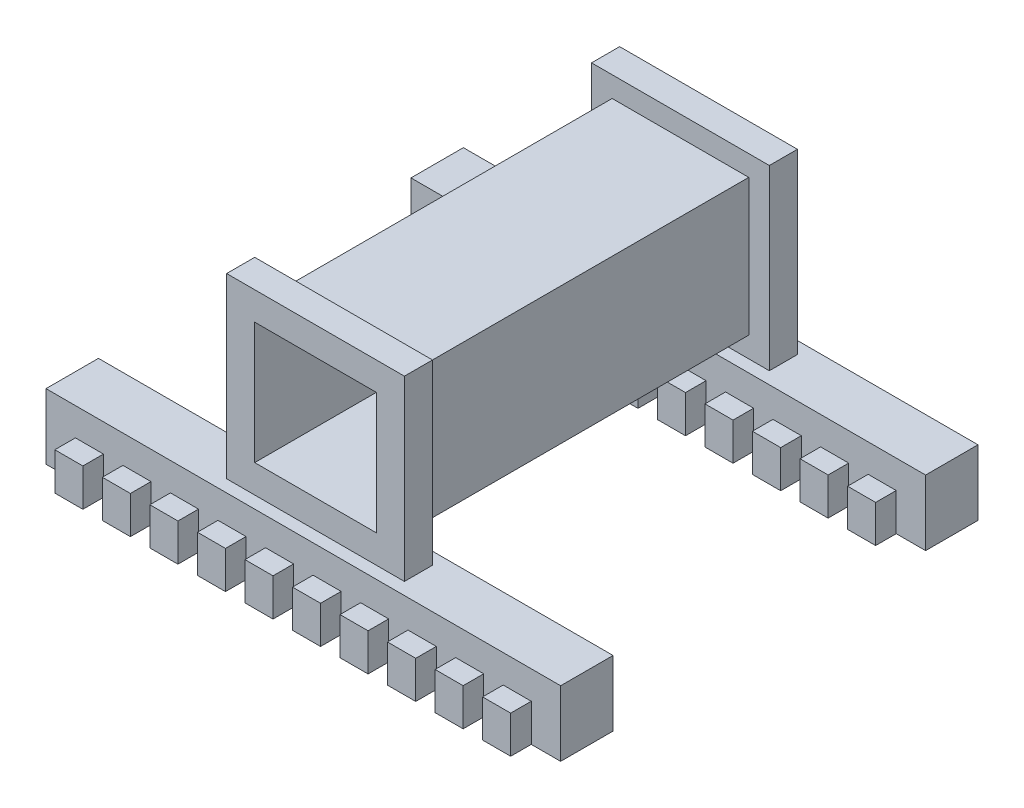
SolidWorks part; units mm, degrees
ref_plane "前视基准面" through (0, 0, 0) normal (0, 0, 1) x (1, 0, 0)
ref_plane "上视基准面" through (0, 0, 0) normal (0, 1, 0) x (1, 0, 0)
ref_plane "右视基准面" through (0, 0, 0) normal (1, 0, 0) x (0, 0, -1)
sketch "草图1" plane through (0, 0, 0) normal (0, 0, 1) x (1, 0, 0)
  line L0 (-9.5, 9.5) -> (9.5, 9.5)
  line L1 (-6.5, -6.5) -> (6.5, -6.5)
  line L2 (-6.5, -6.5) -> (-6.5, 6.5)
  line L3 (-6.5, 6.5) -> (6.5, 6.5)
  line L4 (6.5, -6.5) -> (6.5, 6.5)
  line L5 (-6.5, -6.5) -> (6.5, 6.5) construction
  line L6 (-6.5, 6.5) -> (6.5, -6.5) construction
  line L7 (9.5, -9.5) -> (9.5, 9.5)
  line L8 (-9.5, -9.5) -> (9.5, -9.5)
  line L9 (-9.5, -9.5) -> (-9.5, 9.5)
  line L10 (-7.3, 7.3) -> (7.3, 7.3)
  line L11 (7.3, -7.3) -> (7.3, 7.3)
  line L12 (-7.3, -7.3) -> (7.3, -7.3)
  line L13 (-7.3, -7.3) -> (-7.3, 7.3)
  line L15 (-27.5, -9.5) -> (27.5, -9.5)
  line L16 (-27.5, -9.5) -> (-27.5, -16.5)
  line L17 (-27.5, -16.5) -> (27.5, -16.5)
  line L18 (27.5, -9.5) -> (27.5, -16.5)
  point P0 (0, 0)
  dimension "D1" = 3
  dimension "D2" = 0.8
extrude "凸台-拉伸1" add sketch "草图1" along normal mid plane 42 contours L18 L15 L8 L16 L17 | L9 L8 L7 L0 L12 L13 L10 L11 | L13 L10 L11 L12 region at (0, 9.2313, 0) region at (0, -13, 0)
extrude "切除-拉伸1" cut sketch "草图1<3>" against normal mid plane 42 contours L2 L3 L4 L1
sketch "草图1<3>" plane through (0, 0, 0) normal (0, 0, 1) x (1, 0, 0) same geometry as "草图1"
sketch "草图2" plane through (0, 0, 0) normal (1, 0, 0) x (0, 0, -1)
  line L0 (21, -16.5) -> (21, -9.5) construction
  line L1 (21, -9.5) -> (-21, -9.5) construction
  line L2 (-21, -9.5) -> (-21, -16.5) construction
  line L3 (-21, -16.5) -> (21, -16.5) construction
  line L4 (21, -9.5) -> (21, 9.5) construction
  line L5 (21, 9.5) -> (-21, 9.5) construction
  line L6 (-21, 9.5) -> (-21, -9.5) construction
  line L7 (-21, -9.5) -> (21, -9.5) construction
  line L8 (21, -16.5) -> (21, -9.5)
  line L9 (21, -9.5) -> (-21, -9.5)
  line L10 (-21, -9.5) -> (-21, -16.5)
  line L11 (-21, -16.5) -> (21, -16.5)
  line L12 (21, -9.5) -> (21, 9.5)
  line L13 (21, 9.5) -> (-21, 9.5)
  line L14 (-21, 9.5) -> (-21, -9.5)
  line L15 (-21, -9.5) -> (21, -9.5)
extrude "切除-拉伸6" cut sketch "草图1<12>" against normal mid plane 36 contours L1 L4 L3 L2 | L9 L0 L7 L8 | L13 L10 L11 L12 region at (0, 0, 0)
sketch "草图1<12>" plane through (0, 0, 0) normal (0, 0, 1) x (1, 0, 0) same geometry as "草图1"
extrude "切除-拉伸7" cut sketch "草图1<13>" against normal mid plane 29 contours L18 L15 L8 L16 L17 region at (0, -13, 0)
sketch "草图1<13>" plane through (0, 0, 0) normal (0, 0, 1) x (1, 0, 0) same geometry as "草图1"
sketch "草图4" plane through (0, 0, 0) normal (1, 0, 0) x (0, 0, -1)
  line L0 (-21, -9.5) -> (-14.5, -9.5) construction
  line L1 (-14.5, -9.5) -> (-14.5, -16.5) construction
  line L2 (-14.5, -16.5) -> (-21, -16.5) construction
  line L3 (-21, -16.5) -> (-21, -9.5) construction
  line L4 (-18, 9.5) -> (-18, -9.5) construction
  line L5 (-18, -9.5) -> (-21, -9.5) construction
  line L6 (-21, -9.5) -> (-21, 9.5) construction
  line L7 (-21, 9.5) -> (-18, 9.5) construction
  line L8 (-18, -7.3) -> (-18, 7.3) construction
  line L9 (-18, 7.3) -> (18, 7.3) construction
  line L10 (18, 7.3) -> (18, -7.3) construction
  line L11 (18, -7.3) -> (-18, -7.3) construction
  line L12 (21, -9.5) -> (18, -9.5) construction
  line L13 (18, -9.5) -> (18, 9.5) construction
  line L14 (18, 9.5) -> (21, 9.5) construction
  line L15 (21, 9.5) -> (21, -9.5) construction
  line L16 (14.5, -16.5) -> (14.5, -9.5) construction
  line L17 (14.5, -9.5) -> (21, -9.5) construction
  line L18 (21, -9.5) -> (21, -16.5) construction
  line L19 (21, -16.5) -> (14.5, -16.5) construction
  line L20 (-21, -9.5) -> (-14.5, -9.5)
  line L21 (-14.5, -9.5) -> (-14.5, -16.5)
  line L22 (-14.5, -16.5) -> (-21, -16.5)
  line L23 (-21, -16.5) -> (-21, -9.5)
  line L24 (-18, 9.5) -> (-18, -9.5)
  line L25 (-18, -9.5) -> (-21, -9.5)
  line L26 (-21, -9.5) -> (-21, 9.5)
  line L27 (-21, 9.5) -> (-18, 9.5)
  line L28 (-18, -7.3) -> (-18, 7.3)
  line L29 (-18, 7.3) -> (18, 7.3)
  line L30 (18, 7.3) -> (18, -7.3)
  line L31 (18, -7.3) -> (-18, -7.3)
  line L32 (21, -9.5) -> (18, -9.5)
  line L33 (18, -9.5) -> (18, 9.5)
  line L34 (18, 9.5) -> (21, 9.5)
  line L35 (21, 9.5) -> (21, -9.5)
  line L36 (14.5, -16.5) -> (14.5, -9.5)
  line L37 (14.5, -9.5) -> (21, -9.5)
  line L38 (21, -9.5) -> (21, -16.5)
  line L39 (21, -16.5) -> (14.5, -16.5)
  line L40 (21, -9.5) -> (24.5, -9.5)
  line L41 (24.5, -9.5) -> (24.5, -16.5)
  line L42 (24.5, -16.5) -> (21, -16.5)
  line L43 (-21, -16.5) -> (-24.5049, -16.5)
  line L44 (-24.5049, -16.5) -> (-24.5049, -9.5)
  line L45 (-24.5049, -9.5) -> (-21, -9.5)
extrude "凸台-拉伸2" add sketch "草图4" along normal mid plane 55 contours L42 L41 L40 L38 | L45 L44 L43 L23 region at (0, -13, 22.7525) region at (0, -13, -22.75)
sketch "草图5" plane through (0, 0, -24.5) normal (0, 0, -1) x (-1, 0, 0)
  line L4 (27.5, -16.5) -> (27.5, -9.5)
  line L5 (27.5, -9.5) -> (-27.5, -9.5)
  line L6 (-27.5, -9.5) -> (-27.5, -16.5)
  line L7 (-27.5, -16.5) -> (27.5, -16.5)
  line L8 (27.5, -16.5) -> (27.5, -9.5)
  line L9 (27.5, -9.5) -> (-27.5, -9.5)
  line L10 (-27.5, -9.5) -> (-27.5, -16.5)
  line L12 (-9.5, -9.5) -> (9.5, -9.5)
  line L13 (-9.5, 9.5) -> (-9.5, -9.5)
  line L14 (9.5, 9.5) -> (-9.5, 9.5)
  line L15 (9.5, -9.5) -> (9.5, 9.5)
  line L16 (-9.5, -9.5) -> (9.5, -9.5)
  line L17 (-9.5, 9.5) -> (-9.5, -9.5)
  line L18 (9.5, 9.5) -> (-9.5, 9.5)
  line L19 (9.5, -9.5) -> (9.5, 9.5)
  line L24 (-27.5, -16.5) -> (27.5, -16.5) construction
  line L37 (22.8593, -16.5) -> (27.5, -16.5)
  line L50 (-21.36, -16.5) -> (-24.36, -16.5)
  line L55 (-11.187, -12.5036) -> (-14.213, -12.5036)
  line L56 (-11.187, -12.5036) -> (-11.187, -16.5)
  line L61 (-6.12, -16.5) -> (-9.12, -16.5)
  line L62 (-6.12, -16.5) -> (-6.12, -12.5036)
  line L68 (-1.04, -16.4978) -> (-4.04, -16.4978)
  line L86 (9.12, -16.5) -> (6.12, -16.5)
  line L91 (9.12, -16.5) -> (9.12, -12.5)
  line L92 (9.12, -12.5) -> (6.12, -12.5)
  line L97 (6.12, -16.5) -> (6.12, -12.5)
  line L98 (9.12, -16.5) -> (6.12, -12.5) construction
  line L103 (-21.36, -16.5) -> (-21.36, -12.5036)
  line L104 (-21.36, -12.5036) -> (-24.36, -12.5036)
  line L105 (-24.36, -16.5) -> (-24.36, -12.5036)
  line L106 (-21.36, -16.5) -> (-24.36, -12.5036) construction
  line L107 (-21.36, -12.5036) -> (-24.36, -16.5) construction
  line L108 (-19.28, -16.5) -> (-16.28, -16.5)
  line L109 (-19.28, -16.5) -> (-19.28, -12.5036)
  line L110 (-19.28, -12.5036) -> (-16.28, -12.5036)
  line L111 (-16.28, -16.5) -> (-16.28, -12.5036)
  line L112 (-19.28, -16.5) -> (-16.28, -12.5036) construction
  line L113 (-19.28, -12.5036) -> (-16.28, -16.5) construction
  line L114 (-11.187, -16.5) -> (-14.213, -16.5)
  line L115 (-14.213, -12.5036) -> (-14.213, -16.5)
  line L116 (-11.187, -12.5036) -> (-14.213, -16.5) construction
  line L117 (-11.187, -16.5) -> (-14.213, -12.5036) construction
  line L118 (-6.12, -12.5036) -> (-9.12, -12.5036)
  line L119 (-9.12, -16.5) -> (-9.12, -12.5036)
  line L120 (-6.12, -16.5) -> (-9.12, -12.5036) construction
  line L121 (-6.12, -12.5036) -> (-9.12, -16.5) construction
  line L122 (-1.04, -16.4978) -> (-1.04, -12.4978)
  line L123 (-1.04, -12.4978) -> (-4.04, -12.4978)
  line L124 (-4.04, -16.4978) -> (-4.04, -12.4978)
  line L125 (-1.04, -16.4978) -> (-4.04, -12.4978) construction
  line L126 (-1.04, -12.4978) -> (-4.04, -16.4978) construction
  line L128 (9.12, -12.5) -> (6.12, -16.5) construction
  line L129 (4.04, -16.5) -> (1.038, -16.5)
  line L130 (4.04, -16.5) -> (4.04, -12.4956)
  line L131 (4.04, -12.4956) -> (1.038, -12.4956)
  line L132 (1.038, -16.5) -> (1.038, -12.4956)
  line L133 (4.04, -16.5) -> (1.038, -12.4956) construction
  line L134 (4.04, -12.4956) -> (1.038, -16.5) construction
  line L135 (14.2014, -16.5) -> (11.1986, -16.5)
  line L136 (14.2014, -16.5) -> (14.2014, -12.5)
  line L137 (14.2014, -12.5) -> (11.1986, -12.5)
  line L138 (11.1986, -16.5) -> (11.1986, -12.5)
  line L139 (14.2014, -16.5) -> (11.1986, -12.5) construction
  line L140 (14.2014, -12.5) -> (11.1986, -16.5) construction
  line L141 (19.28, -16.4935) -> (16.28, -16.4935)
  line L142 (19.28, -16.4935) -> (19.28, -12.4935)
  line L143 (19.28, -12.4935) -> (16.28, -12.4935)
  line L144 (16.28, -16.4935) -> (16.28, -12.4935)
  line L145 (19.28, -16.4935) -> (16.28, -12.4935) construction
  line L146 (19.28, -12.4935) -> (16.28, -16.4935) construction
  line L151 (24.3586, -16.5) -> (21.36, -16.5)
  line L152 (24.3586, -16.5) -> (24.3586, -12.487)
  line L153 (24.3586, -12.487) -> (21.36, -12.487)
  line L154 (21.36, -16.5) -> (21.36, -12.487)
  line L155 (24.3586, -16.5) -> (21.36, -12.487) construction
  line L156 (24.3586, -12.487) -> (21.36, -16.5) construction
  point P6 (-22.86, -14.5018)
  point P33 (-17.78, -14.5018)
  point P35 (-17.78, -14.5018)
  point P39 (-12.7, -14.5018)
  point P40 (-12.7, -14.5018)
  point P45 (-7.62, -14.5018)
  point P50 (-2.54, -14.4978)
  point P55 (2.539, -14.4978)
  point P60 (7.62, -14.5)
  point P65 (12.7, -14.5)
  point P70 (17.78, -14.4935)
  point P75 (22.8593, -14.4935)
  line M42 (27.5, -16.5) -> (27.5, -9.5)
  line M43 (27.5, -9.5) -> (-27.5, -9.5)
  line M44 (-27.5, -9.5) -> (-27.5, -16.5)
  line M45 (-27.5, -16.5) -> (27.5, -16.5)
  dimension "D1" = 0
  dimension "D2" = 0
extrude "切除-拉伸9" cut sketch "草图5" against normal blind 2.2 contours L154 L153 L152 L37 L9 L105 L104 L103 L109 L110 L111 L115 L55 L56 L119 L118 L62 L132 L131 L130 L97 L92 L91 L138 L137 L136 L68 L124 L123 L122 L141 L144 L143 L142 M45 M42 M43 M44 region at (0.0011, -12.3202, -24.5)
sketch "草图6" plane through (0, 0, -14.5) normal (0, 0, 1) x (1, 0, 0)
  line L0 (-16.28, -16.4935) -> (-19.28, -16.4935) construction
  line L1 (-19.28, -16.4935) -> (-19.28, -12.4935) construction
  line L2 (-19.28, -12.4935) -> (-16.28, -12.4935) construction
  line L3 (-16.28, -12.4935) -> (-16.28, -16.4935) construction
  line L4 (27.5, -16.5) -> (27.5, -9.5)
  line L5 (27.5, -9.5) -> (-27.5, -9.5)
  line L6 (-27.5, -9.5) -> (-27.5, -16.5)
  line L7 (-27.5, -16.5) -> (27.5, -16.5)
  line L8 (27.5, -16.5) -> (27.5, -9.5)
  line L9 (27.5, -9.5) -> (-27.5, -9.5)
  line L10 (-27.5, -9.5) -> (-27.5, -16.5)
  line L11 (-27.5, -16.5) -> (27.5, -16.5)
  line L12 (-21.36, -16.5) -> (-24.3586, -16.5) construction
  line L13 (-24.3586, -16.5) -> (-24.3586, -12.487) construction
  line L14 (-24.3586, -12.487) -> (-21.36, -12.487) construction
  line L15 (-21.36, -12.487) -> (-21.36, -16.5) construction
  line L16 (-11.1986, -16.5) -> (-14.2014, -16.5) construction
  line L17 (-14.2014, -16.5) -> (-14.2014, -12.5) construction
  line L18 (-14.2014, -12.5) -> (-11.1986, -12.5) construction
  line L19 (-11.1986, -12.5) -> (-11.1986, -16.5) construction
  line L20 (-6.12, -16.5) -> (-9.12, -16.5) construction
  line L21 (-9.12, -16.5) -> (-9.12, -12.5) construction
  line L22 (-9.12, -12.5) -> (-6.12, -12.5) construction
  line L23 (-6.12, -12.5) -> (-6.12, -16.5) construction
  line L24 (-1.038, -16.5) -> (-4.04, -16.5) construction
  line L25 (-4.04, -16.5) -> (-4.04, -12.4956) construction
  line L26 (-4.04, -12.4956) -> (-1.038, -12.4956) construction
  line L27 (-1.038, -12.4956) -> (-1.038, -16.5) construction
  line L28 (4.04, -16.4978) -> (1.04, -16.4978) construction
  line L29 (1.04, -16.4978) -> (1.04, -12.4978) construction
  line L30 (1.04, -12.4978) -> (4.04, -12.4978) construction
  line L31 (4.04, -12.4978) -> (4.04, -16.4978) construction
  line L32 (9.12, -16.5) -> (6.12, -16.5) construction
  line L33 (6.12, -16.5) -> (6.12, -12.5036) construction
  line L34 (6.12, -12.5036) -> (9.12, -12.5036) construction
  line L35 (9.12, -12.5036) -> (9.12, -16.5) construction
  line L36 (11.187, -16.5) -> (11.187, -12.5036) construction
  line L37 (11.187, -12.5036) -> (14.213, -12.5036) construction
  line L38 (14.213, -12.5036) -> (14.213, -16.5) construction
  line L39 (14.213, -16.5) -> (11.187, -16.5) construction
  line L40 (19.28, -16.5) -> (16.28, -16.5) construction
  line L41 (16.28, -16.5) -> (16.28, -12.5036) construction
  line L42 (16.28, -12.5036) -> (19.28, -12.5036) construction
  line L43 (19.28, -12.5036) -> (19.28, -16.5) construction
  line L44 (24.36, -16.5) -> (21.36, -16.5) construction
  line L45 (21.36, -16.5) -> (21.36, -12.5036) construction
  line L46 (21.36, -12.5036) -> (24.36, -12.5036) construction
  line L47 (24.36, -12.5036) -> (24.36, -16.5) construction
  line L48 (-16.28, -16.4935) -> (-19.28, -16.4935)
  line L49 (-19.28, -16.4935) -> (-19.28, -12.4935)
  line L50 (-19.28, -12.4935) -> (-16.28, -12.4935)
  line L51 (-16.28, -12.4935) -> (-16.28, -16.4935)
  line L52 (-21.36, -16.5) -> (-24.3586, -16.5)
  line L53 (-24.3586, -16.5) -> (-24.3586, -12.487)
  line L54 (-24.3586, -12.487) -> (-21.36, -12.487)
  line L55 (-21.36, -12.487) -> (-21.36, -16.5)
  line L56 (-11.1986, -16.5) -> (-14.2014, -16.5)
  line L57 (-14.2014, -16.5) -> (-14.2014, -12.5)
  line L58 (-14.2014, -12.5) -> (-11.1986, -12.5)
  line L59 (-11.1986, -12.5) -> (-11.1986, -16.5)
  line L60 (-6.12, -16.5) -> (-9.12, -16.5)
  line L61 (-9.12, -16.5) -> (-9.12, -12.5)
  line L62 (-9.12, -12.5) -> (-6.12, -12.5)
  line L63 (-6.12, -12.5) -> (-6.12, -16.5)
  line L64 (-1.038, -16.5) -> (-4.04, -16.5)
  line L65 (-4.04, -16.5) -> (-4.04, -12.4956)
  line L66 (-4.04, -12.4956) -> (-1.038, -12.4956)
  line L67 (-1.038, -12.4956) -> (-1.038, -16.5)
  line L68 (4.04, -16.4978) -> (1.04, -16.4978)
  line L69 (1.04, -16.4978) -> (1.04, -12.4978)
  line L70 (1.04, -12.4978) -> (4.04, -12.4978)
  line L71 (4.04, -12.4978) -> (4.04, -16.4978)
  line L72 (9.12, -16.5) -> (6.12, -16.5)
  line L73 (6.12, -16.5) -> (6.12, -12.5036)
  line L74 (6.12, -12.5036) -> (9.12, -12.5036)
  line L75 (9.12, -12.5036) -> (9.12, -16.5)
  line L76 (11.187, -16.5) -> (11.187, -12.5036)
  line L77 (11.187, -12.5036) -> (14.213, -12.5036)
  line L78 (14.213, -12.5036) -> (14.213, -16.5)
  line L79 (14.213, -16.5) -> (11.187, -16.5)
  line L80 (19.28, -16.5) -> (16.28, -16.5)
  line L81 (16.28, -16.5) -> (16.28, -12.5036)
  line L82 (16.28, -12.5036) -> (19.28, -12.5036)
  line L83 (19.28, -12.5036) -> (19.28, -16.5)
  line L84 (24.36, -16.5) -> (21.36, -16.5)
  line L85 (21.36, -16.5) -> (21.36, -12.5036)
  line L86 (21.36, -12.5036) -> (24.36, -12.5036)
  line L87 (24.36, -12.5036) -> (24.36, -16.5)
  line M5 (27.5, -16.5) -> (27.5, -9.5)
  line M6 (27.5, -9.5) -> (-27.5, -9.5)
  line M7 (-27.5, -9.5) -> (-27.5, -16.5)
  line M8 (-27.5, -16.5) -> (27.5, -16.5)
  dimension "D1" = 0
extrude "切除-拉伸10" cut sketch "草图6" against normal blind 2.2 contours L86 L87 L53 L54 L55 L57 L58 L59 L61 L62 L63 L65 L66 L67 L73 L74 L75 L76 L77 L78 L81 L82 L83 L85 L50 L51 L48 L49 L70 L71 L68 L69 M8 M5 M6 M7 region at (0.0011, -12.3202, -14.5)
sketch "草图7" plane through (0, 0, 14.5) normal (0, 0, -1) x (-1, 0, 0)
  line L0 (-24.36, -16.5) -> (-21.36, -16.5) construction
  line L1 (-21.36, -16.5) -> (-21.36, -12.5036) construction
  line L2 (-21.36, -12.5036) -> (-24.36, -12.5036) construction
  line L3 (-24.36, -12.5036) -> (-24.36, -16.5) construction
  line L4 (-27.5, -9.5) -> (-27.5, -16.5)
  line L5 (-27.5, -16.5) -> (27.5, -16.5)
  line L6 (27.5, -16.5) -> (27.5, -9.5)
  line L7 (27.5, -9.5) -> (-27.5, -9.5)
  line L8 (-27.5, -9.5) -> (-27.5, -16.5)
  line L9 (-27.5, -16.5) -> (27.5, -16.5)
  line L10 (27.5, -16.5) -> (27.5, -9.5)
  line L11 (27.5, -9.5) -> (-27.5, -9.5)
  line L12 (-19.28, -16.5) -> (-16.28, -16.5) construction
  line L13 (-16.28, -16.5) -> (-16.28, -12.5036) construction
  line L14 (-16.28, -12.5036) -> (-19.28, -12.5036) construction
  line L15 (-19.28, -12.5036) -> (-19.28, -16.5) construction
  line L16 (-11.187, -16.5) -> (-11.187, -12.5036) construction
  line L17 (-11.187, -12.5036) -> (-14.213, -12.5036) construction
  line L18 (-14.213, -12.5036) -> (-14.213, -16.5) construction
  line L19 (-14.213, -16.5) -> (-11.187, -16.5) construction
  line L20 (-9.12, -16.5) -> (-6.12, -16.5) construction
  line L21 (-6.12, -16.5) -> (-6.12, -12.5036) construction
  line L22 (-6.12, -12.5036) -> (-9.12, -12.5036) construction
  line L23 (-9.12, -12.5036) -> (-9.12, -16.5) construction
  line L24 (-4.04, -16.4978) -> (-1.04, -16.4978) construction
  line L25 (-1.04, -16.4978) -> (-1.04, -12.4978) construction
  line L26 (-1.04, -12.4978) -> (-4.04, -12.4978) construction
  line L27 (-4.04, -12.4978) -> (-4.04, -16.4978) construction
  line L28 (1.038, -16.5) -> (4.04, -16.5) construction
  line L29 (4.04, -16.5) -> (4.04, -12.4956) construction
  line L30 (4.04, -12.4956) -> (1.038, -12.4956) construction
  line L31 (1.038, -12.4956) -> (1.038, -16.5) construction
  line L32 (6.12, -16.5) -> (9.12, -16.5) construction
  line L33 (9.12, -16.5) -> (9.12, -12.5) construction
  line L34 (9.12, -12.5) -> (6.12, -12.5) construction
  line L35 (6.12, -12.5) -> (6.12, -16.5) construction
  line L36 (11.1986, -16.5) -> (14.2014, -16.5) construction
  line L37 (14.2014, -16.5) -> (14.2014, -12.5) construction
  line L38 (14.2014, -12.5) -> (11.1986, -12.5) construction
  line L39 (11.1986, -12.5) -> (11.1986, -16.5) construction
  line L40 (16.28, -16.4935) -> (19.28, -16.4935) construction
  line L41 (19.28, -16.4935) -> (19.28, -12.4935) construction
  line L42 (19.28, -12.4935) -> (16.28, -12.4935) construction
  line L43 (16.28, -12.4935) -> (16.28, -16.4935) construction
  line L44 (21.36, -16.5) -> (24.3586, -16.5) construction
  line L45 (24.3586, -16.5) -> (24.3586, -12.487) construction
  line L46 (24.3586, -12.487) -> (21.36, -12.487) construction
  line L47 (21.36, -12.487) -> (21.36, -16.5) construction
  line L48 (-24.36, -16.5) -> (-21.36, -16.5)
  line L49 (-21.36, -16.5) -> (-21.36, -12.5036)
  line L50 (-21.36, -12.5036) -> (-24.36, -12.5036)
  line L51 (-24.36, -12.5036) -> (-24.36, -16.5)
  line L52 (-19.28, -16.5) -> (-16.28, -16.5)
  line L53 (-16.28, -16.5) -> (-16.28, -12.5036)
  line L54 (-16.28, -12.5036) -> (-19.28, -12.5036)
  line L55 (-19.28, -12.5036) -> (-19.28, -16.5)
  line L56 (-11.187, -16.5) -> (-11.187, -12.5036)
  line L57 (-11.187, -12.5036) -> (-14.213, -12.5036)
  line L58 (-14.213, -12.5036) -> (-14.213, -16.5)
  line L59 (-14.213, -16.5) -> (-11.187, -16.5)
  line L60 (-9.12, -16.5) -> (-6.12, -16.5)
  line L61 (-6.12, -16.5) -> (-6.12, -12.5036)
  line L62 (-6.12, -12.5036) -> (-9.12, -12.5036)
  line L63 (-9.12, -12.5036) -> (-9.12, -16.5)
  line L64 (-4.04, -16.4978) -> (-1.04, -16.4978)
  line L65 (-1.04, -16.4978) -> (-1.04, -12.4978)
  line L66 (-1.04, -12.4978) -> (-4.04, -12.4978)
  line L67 (-4.04, -12.4978) -> (-4.04, -16.4978)
  line L68 (1.038, -16.5) -> (4.04, -16.5)
  line L69 (4.04, -16.5) -> (4.04, -12.4956)
  line L70 (4.04, -12.4956) -> (1.038, -12.4956)
  line L71 (1.038, -12.4956) -> (1.038, -16.5)
  line L72 (6.12, -16.5) -> (9.12, -16.5)
  line L73 (9.12, -16.5) -> (9.12, -12.5)
  line L74 (9.12, -12.5) -> (6.12, -12.5)
  line L75 (6.12, -12.5) -> (6.12, -16.5)
  line L76 (11.1986, -16.5) -> (14.2014, -16.5)
  line L77 (14.2014, -16.5) -> (14.2014, -12.5)
  line L78 (14.2014, -12.5) -> (11.1986, -12.5)
  line L79 (11.1986, -12.5) -> (11.1986, -16.5)
  line L80 (16.28, -16.4935) -> (19.28, -16.4935)
  line L81 (19.28, -16.4935) -> (19.28, -12.4935)
  line L82 (19.28, -12.4935) -> (16.28, -12.4935)
  line L83 (16.28, -12.4935) -> (16.28, -16.4935)
  line L84 (21.36, -16.5) -> (24.3586, -16.5)
  line L85 (24.3586, -16.5) -> (24.3586, -12.487)
  line L86 (24.3586, -12.487) -> (21.36, -12.487)
  line L87 (21.36, -12.487) -> (21.36, -16.5)
  line M5 (-27.5, -9.5) -> (-27.5, -16.5)
  line M6 (-27.5, -16.5) -> (27.5, -16.5)
  line M7 (27.5, -16.5) -> (27.5, -9.5)
  line M8 (27.5, -9.5) -> (-27.5, -9.5)
  dimension "D1" = 0
extrude "切除-拉伸11" cut sketch "草图7" against normal blind 2.2 contours L87 L86 L85 L9 L51 L50 L49 L55 L54 L53 L58 L57 L56 L63 L62 L61 L71 L70 L69 L75 L74 L73 L79 L78 L77 L83 L82 L81 L80 L67 L66 L65 L64 M7 M8 M5 M6 region at (0.0011, -12.3202, 14.5)
sketch "草图8" plane through (0, 0, 24.5049) normal (0, 0, 1) x (1, 0, 0)
  line L0 (21.36, -12.5036) -> (21.36, -16.5) construction
  line L1 (21.36, -16.5) -> (24.36, -16.5) construction
  line L2 (24.36, -16.5) -> (24.36, -12.5036) construction
  line L3 (24.36, -12.5036) -> (21.36, -12.5036) construction
  line L4 (-27.5, -9.5) -> (-27.5, -16.5)
  line L5 (-27.5, -16.5) -> (27.5, -16.5)
  line L6 (27.5, -16.5) -> (27.5, -9.5)
  line L7 (27.5, -9.5) -> (-27.5, -9.5)
  line L8 (-27.5, -9.5) -> (-27.5, -16.5)
  line L9 (-27.5, -16.5) -> (27.5, -16.5)
  line L10 (27.5, -16.5) -> (27.5, -9.5)
  line L11 (27.5, -9.5) -> (-27.5, -9.5)
  line L12 (19.28, -16.5) -> (19.28, -12.5036) construction
  line L13 (19.28, -12.5036) -> (16.28, -12.5036) construction
  line L14 (16.28, -12.5036) -> (16.28, -16.5) construction
  line L15 (16.28, -16.5) -> (19.28, -16.5) construction
  line L16 (14.213, -16.5) -> (14.213, -12.5036) construction
  line L17 (14.213, -12.5036) -> (11.187, -12.5036) construction
  line L18 (11.187, -12.5036) -> (11.187, -16.5) construction
  line L19 (11.187, -16.5) -> (14.213, -16.5) construction
  line L20 (9.12, -16.5) -> (9.12, -12.5036) construction
  line L21 (9.12, -12.5036) -> (6.12, -12.5036) construction
  line L22 (6.12, -12.5036) -> (6.12, -16.5) construction
  line L23 (6.12, -16.5) -> (9.12, -16.5) construction
  line L24 (4.04, -12.4978) -> (1.04, -12.4978) construction
  line L25 (1.04, -12.4978) -> (1.04, -16.4978) construction
  line L26 (1.04, -16.4978) -> (4.04, -16.4978) construction
  line L27 (4.04, -16.4978) -> (4.04, -12.4978) construction
  line L28 (-1.038, -16.5) -> (-1.038, -12.4956) construction
  line L29 (-1.038, -12.4956) -> (-4.04, -12.4956) construction
  line L30 (-4.04, -12.4956) -> (-4.04, -16.5) construction
  line L31 (-4.04, -16.5) -> (-1.038, -16.5) construction
  line L32 (-6.12, -16.5) -> (-6.12, -12.5) construction
  line L33 (-6.12, -12.5) -> (-9.12, -12.5) construction
  line L34 (-9.12, -12.5) -> (-9.12, -16.5) construction
  line L35 (-9.12, -16.5) -> (-6.12, -16.5) construction
  line L36 (-11.1986, -16.5) -> (-11.1986, -12.5) construction
  line L37 (-11.1986, -12.5) -> (-14.2014, -12.5) construction
  line L38 (-14.2014, -12.5) -> (-14.2014, -16.5) construction
  line L39 (-14.2014, -16.5) -> (-11.1986, -16.5) construction
  line L40 (-16.28, -12.4935) -> (-19.28, -12.4935) construction
  line L41 (-19.28, -12.4935) -> (-19.28, -16.4935) construction
  line L42 (-19.28, -16.4935) -> (-16.28, -16.4935) construction
  line L43 (-16.28, -16.4935) -> (-16.28, -12.4935) construction
  line L44 (-21.36, -16.5) -> (-21.36, -12.487) construction
  line L45 (-21.36, -12.487) -> (-24.3586, -12.487) construction
  line L46 (-24.3586, -12.487) -> (-24.3586, -16.5) construction
  line L47 (-24.3586, -16.5) -> (-21.36, -16.5) construction
  line L48 (21.36, -12.5036) -> (21.36, -16.5)
  line L49 (21.36, -16.5) -> (24.36, -16.5)
  line L50 (24.36, -16.5) -> (24.36, -12.5036)
  line L51 (24.36, -12.5036) -> (21.36, -12.5036)
  line L52 (19.28, -16.5) -> (19.28, -12.5036)
  line L53 (19.28, -12.5036) -> (16.28, -12.5036)
  line L54 (16.28, -12.5036) -> (16.28, -16.5)
  line L55 (16.28, -16.5) -> (19.28, -16.5)
  line L56 (14.213, -16.5) -> (14.213, -12.5036)
  line L57 (14.213, -12.5036) -> (11.187, -12.5036)
  line L58 (11.187, -12.5036) -> (11.187, -16.5)
  line L59 (11.187, -16.5) -> (14.213, -16.5)
  line L60 (9.12, -16.5) -> (9.12, -12.5036)
  line L61 (9.12, -12.5036) -> (6.12, -12.5036)
  line L62 (6.12, -12.5036) -> (6.12, -16.5)
  line L63 (6.12, -16.5) -> (9.12, -16.5)
  line L64 (4.04, -12.4978) -> (1.04, -12.4978)
  line L65 (1.04, -12.4978) -> (1.04, -16.4978)
  line L66 (1.04, -16.4978) -> (4.04, -16.4978)
  line L67 (4.04, -16.4978) -> (4.04, -12.4978)
  line L68 (-1.038, -16.5) -> (-1.038, -12.4956)
  line L69 (-1.038, -12.4956) -> (-4.04, -12.4956)
  line L70 (-4.04, -12.4956) -> (-4.04, -16.5)
  line L71 (-4.04, -16.5) -> (-1.038, -16.5)
  line L72 (-6.12, -16.5) -> (-6.12, -12.5)
  line L73 (-6.12, -12.5) -> (-9.12, -12.5)
  line L74 (-9.12, -12.5) -> (-9.12, -16.5)
  line L75 (-9.12, -16.5) -> (-6.12, -16.5)
  line L76 (-11.1986, -16.5) -> (-11.1986, -12.5)
  line L77 (-11.1986, -12.5) -> (-14.2014, -12.5)
  line L78 (-14.2014, -12.5) -> (-14.2014, -16.5)
  line L79 (-14.2014, -16.5) -> (-11.1986, -16.5)
  line L80 (-16.28, -12.4935) -> (-19.28, -12.4935)
  line L81 (-19.28, -12.4935) -> (-19.28, -16.4935)
  line L82 (-19.28, -16.4935) -> (-16.28, -16.4935)
  line L83 (-16.28, -16.4935) -> (-16.28, -12.4935)
  line L84 (-21.36, -16.5) -> (-21.36, -12.487)
  line L85 (-21.36, -12.487) -> (-24.3586, -12.487)
  line L86 (-24.3586, -12.487) -> (-24.3586, -16.5)
  line L87 (-24.3586, -16.5) -> (-21.36, -16.5)
  line M5 (-27.5, -9.5) -> (-27.5, -16.5)
  line M6 (-27.5, -16.5) -> (27.5, -16.5)
  line M7 (27.5, -16.5) -> (27.5, -9.5)
  line M8 (27.5, -9.5) -> (-27.5, -9.5)
  dimension "D1" = 0
extrude "切除-拉伸12" cut sketch "草图8" against normal blind 2.2 contours L86 L85 L84 L9 L78 L77 L76 L74 L73 L72 L70 L69 L68 L62 L61 L60 L58 L57 L56 L54 L53 L52 L48 L51 L50 L83 L82 L81 L80 L67 L66 L65 L64 M6 M7 M8 M5 region at (0.0011, -12.3202, 24.5049)
sketch "草图9" plane through (0, -16.5, 0) normal (0, -1, 0) x (1, 0, 0)
  line L0 (-22.8593, -24.5) -> (-22.8593, -14.5)
  line L1 (-21.36, -24.5) -> (-24.3586, -24.5) construction
  line L2 (-24.3586, -14.5) -> (-21.36, -14.5) construction
  line L3 (22.86, -24.5) -> (22.86, -14.5)
  line L4 (24.36, -24.5) -> (21.36, -24.5) construction
  line L5 (21.36, -14.5) -> (24.36, -14.5) construction
  line L6 (22.86, -19.5) -> (24.06, -19.5)
  line L7 (-22.8593, -19.5) -> (-24.0593, -19.5)
  line L8 (-24.0593, -19.5) -> (-24.0593, -22.05)
  line L9 (-24.0593, -19.5) -> (-24.0593, -16.95)
  line L10 (-24.0593, -22.05) -> (-22.8593, -22.05)
  line L11 (-22.8593, -22.05) -> (24.06, -22.05)
  line L12 (24.06, -22.05) -> (24.06, -16.95)
  line L13 (24.06, -16.95) -> (-24.0593, -16.95)
  line L14 (-22.8593, 14.5) -> (-22.8593, 24.5049)
  line L15 (-24.3586, 14.5) -> (-21.36, 14.5) construction
  line L16 (-21.36, 24.5049) -> (-24.3586, 24.5049) construction
  line L17 (-27.5, 16.7) -> (-27.5, -16.7)
  line L18 (27.5, 16.7) -> (27.5, -16.7)
  line L19 (27.5, 0) -> (-27.5, 0)
  line L20 (-24.0593, 19.5) -> (-24.0593, 16.95)
  line L21 (24.06, 16.95) -> (-24.0593, 16.95)
  line L22 (24.06, 22.05) -> (24.06, 16.95)
  line L23 (-22.8593, 22.05) -> (24.06, 22.05)
  line L24 (-24.0593, 22.05) -> (-22.8593, 22.05)
  line L25 (-24.0593, 19.5) -> (-24.0593, 22.05)
extrude "切除-拉伸13" cut sketch "草图9" against normal blind 4 contours L3 L13 L0 L11 | L8 L10 L0 L7 | L0 L13 L9 L7 | L12 L13 L3 L6 | L11 L12 L6 L3 | L23 L14 L21 L22 | L25 L20 L21 L14 L24 region at (-23.4593, -16.5, -20.775) region at (0.0003, -16.5, -19.5) region at (-23.4593, -16.5, -18.225) region at (23.46, -16.5, -20.775) region at (23.46, -16.5, -18.225) region at (-23.4593, -16.5, 19.5) region at (0.6003, -16.5, 19.5)
